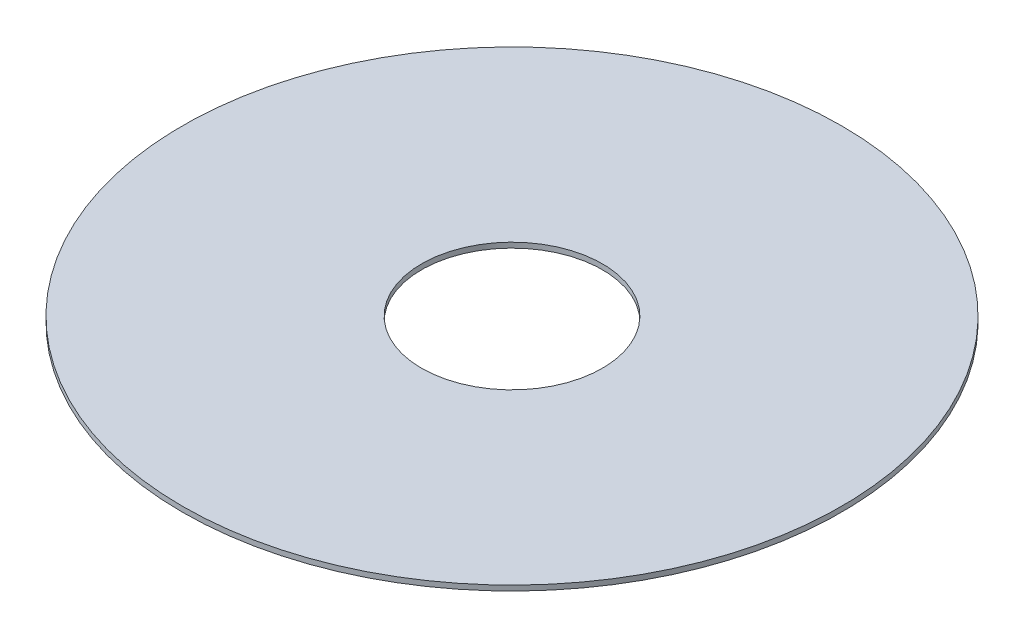
SolidWorks part; units mm, degrees
ref_plane "Ebene vorne" through (0, 0, 0) normal (0, 0, 1) x (1, 0, 0)
ref_plane "Ebene oben" through (0, 0, 0) normal (0, 1, 0) x (1, 0, 0)
ref_plane "Ebene rechts" through (0, 0, 0) normal (1, 0, 0) x (0, 0, -1)
ref_axis "Achse1" through (0, -3.3236, 0) along (0, 1, 0)
sketch "Skizze1" plane through (0, 0, 0) normal (0, 1, 0) x (1, 0, 0)
  circle A0 centre (0, 0) radius 12.75
  circle A1 centre (0, 0) radius 3.5
  dimension "D1" = 7
  dimension "D2" = 25.5
extrude "Aufsatz-Linear austragen1" add sketch "Skizze1" along normal blind 0.1 and the other way blind 0.1
